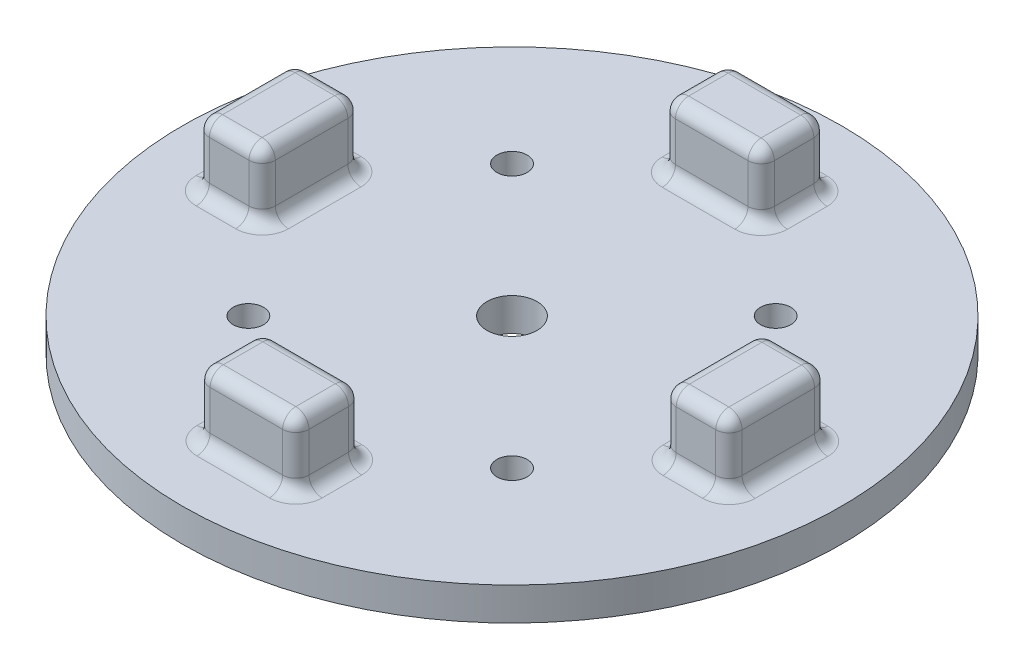
SolidWorks part; units mm, degrees
ref_plane "Front Plane" through (0, 0, 0) normal (0, 0, 1) x (1, 0, 0)
ref_plane "Top Plane" through (0, 0, 0) normal (0, 1, 0) x (1, 0, 0)
ref_plane "Right Plane" through (0, 0, 0) normal (1, 0, 0) x (0, 0, -1)
sketch "Sketch2" plane through (0, 0, 0) normal (0, 1, 0) x (1, 0, 0)
  line L1 (-25.4, 25.4) -> (25.4, 25.4) construction
  line L2 (-25.4, 25.4) -> (-25.4, -25.4) construction
  line L3 (-25.4, -25.4) -> (25.4, -25.4) construction
  line L4 (25.4, 25.4) -> (25.4, -25.4) construction
  line L5 (-25.4, 25.4) -> (25.4, -25.4) construction
  line L6 (-25.4, -25.4) -> (25.4, 25.4) construction
  circle A0 centre (0, 0) radius 63.5
  circle A1 centre (-25.4, 25.4) radius 2.921
  circle A2 centre (25.4, 25.4) radius 2.921
  circle A3 centre (25.4, -25.4) radius 2.921
  circle A4 centre (-25.4, -25.4) radius 2.921
  circle A5 centre (0, 0) radius 4.826
  dimension "D1" = 127
  dimension "D3" = 5.842
  dimension "D4" = 9.652
  dimension "D2" = 50.8
extrude "Boss-Extrude2" add sketch "Sketch2" along normal blind 6.35
sketch "Sketch3" plane through (0, 6.35, 0) normal (0, 1, 0) x (1, 0, 0)
  line L0 (-55, 0) -> (55, 0) construction
  line L1 (-44.9715, 44.831) -> (44.9715, 44.831) construction
  line L2 (-44.9715, 44.831) -> (-44.9715, -44.831) construction
  line L3 (-44.9715, -44.831) -> (44.9715, -44.831) construction
  line L4 (44.9715, 44.831) -> (44.9715, -44.831) construction
  line L5 (-44.9715, 44.831) -> (44.9715, -44.831) construction
  line L6 (-44.9715, -44.831) -> (44.9715, 44.831) construction
  line L7 (-9.525, 38.481) -> (9.525, 38.481)
  line L8 (-9.525, 38.481) -> (-9.525, 51.181)
  line L9 (-9.525, 51.181) -> (9.525, 51.181)
  line L10 (9.525, 38.481) -> (9.525, 51.181)
  line L11 (-9.525, 38.481) -> (9.525, 51.181) construction
  line L12 (-9.525, 51.181) -> (9.525, 38.481) construction
  line L13 (-9.525, -51.181) -> (9.525, -51.181)
  line L14 (9.525, -38.481) -> (9.525, -51.181)
  line L15 (-9.525, -38.481) -> (9.525, -38.481)
  line L16 (-9.525, -38.481) -> (-9.525, -51.181)
  line L17 (-9.525, -51.181) -> (9.525, -38.481) construction
  line L18 (-9.525, -38.481) -> (9.525, -51.181) construction
  line L19 (0, -55) -> (0, 55) construction
  line L20 (-51.3215, 9.525) -> (-38.6215, 9.525)
  line L21 (-51.3215, 9.525) -> (-51.3215, -9.525)
  line L22 (-51.3215, -9.525) -> (-38.6215, -9.525)
  line L23 (-38.6215, 9.525) -> (-38.6215, -9.525)
  line L24 (-51.3215, 9.525) -> (-38.6215, -9.525) construction
  line L25 (-51.3215, -9.525) -> (-38.6215, 9.525) construction
  line L26 (38.6215, 9.525) -> (38.6215, -9.525)
  line L27 (51.3215, -9.525) -> (38.6215, -9.525)
  line L28 (51.3215, 9.525) -> (51.3215, -9.525)
  line L29 (51.3215, 9.525) -> (38.6215, 9.525)
  circle A0 centre (0, 0) radius 63.5 construction
  circle A1 centre (0, 0) radius 63.5 construction
  point P0 (0, 0)
  point P8 (0, 44.831)
  point P19 (0, -44.831)
  point P20 (-44.9715, 0)
  dimension "D1" = 12.7
  dimension "D2" = 19.05
  dimension "D3" = 89.662
extrude "Boss-Extrude3" add sketch "Sketch3" along normal blind 12.7
sketch "Sketch4" plane through (0, 19.05, 0) normal (0, 1, 0) x (1, 0, 0)
  circle A0 centre (0, 0) radius 44.45
  circle A1 centre (0, 0) radius 48.26
  dimension "D1" = 88.9
  dimension "D2" = 3.81
fillet "Fillet1" radius 2.54 48 edges at (51.3215, 6.35, 0) (44.9715, 6.35, -9.525) (44.9715, 6.35, 9.525) (38.6215, 12.7, -9.525) (38.6215, 19.05, 0) (38.6215, 12.7, 9.525) (38.6215, 6.35, 0) (51.3215, 12.7, 9.525) (51.3215, 12.7, -9.525) (-51.3215, 12.7, -9.525) (-51.3215, 12.7, 9.525) (-38.6215, 12.7, 9.525) (-38.6215, 12.7, -9.525) (9.525, 12.7, 51.181) (9.525, 12.7, 38.481) (-9.525, 12.7, 38.481) (-9.525, 12.7, 51.181) (9.525, 12.7, -38.481) (-9.525, 12.7, -38.481) (9.525, 12.7, -51.181) (-9.525, 12.7, -51.181) (0, 6.35, 51.181) (-44.9715, 6.35, 9.525) (0, 6.35, -38.481) (9.525, 6.35, 44.831) (-9.525, 6.35, 44.831) (-38.6215, 6.35, 0) (-51.3215, 6.35, 0) (9.525, 6.35, -44.831) (-9.525, 6.35, -44.831) (0, 19.05, 38.481) (0, 6.35, 38.481) (-44.9715, 6.35, -9.525) (0, 6.35, -51.181) (51.3215, 19.05, 0) (44.9715, 19.05, 9.525) (44.9715, 19.05, -9.525) (-51.3215, 19.05, 0) (0, 19.05, -51.181) (0, 19.05, 51.181) (9.525, 19.05, 44.831) (-9.525, 19.05, 44.831) (-44.9715, 19.05, 9.525) (-38.6215, 19.05, 0) (-44.9715, 19.05, -9.525) (9.525, 19.05, -44.831) (-9.525, 19.05, -44.831) (0, 19.05, -38.481)
